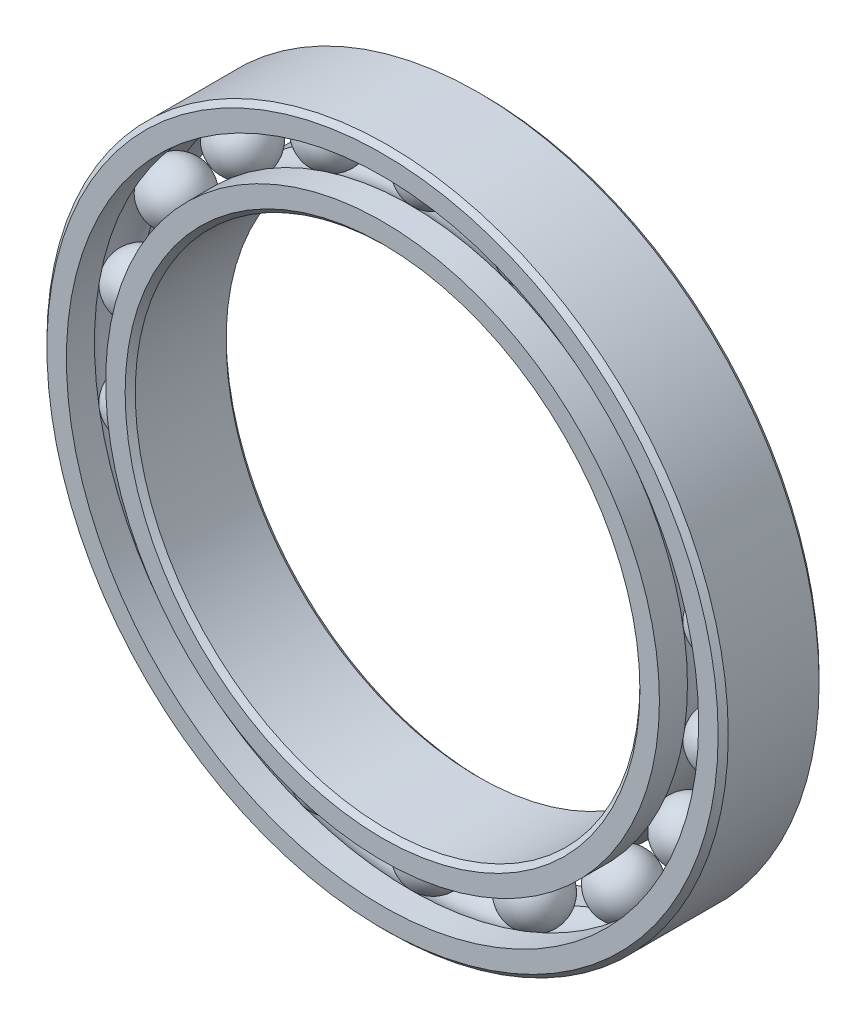
SolidWorks part; units mm, degrees
ref_plane "Front Plane" through (0, 0, 0) normal (0, 0, 1) x (1, 0, 0)
ref_plane "Top Plane" through (0, 0, 0) normal (0, 1, 0) x (1, 0, 0)
ref_plane "Right Plane" through (0, 0, 0) normal (1, 0, 0) x (0, 0, -1)
sketch "Sketch1" plane through (0, 0, 0) normal (0, 0, 1) x (1, 0, 0)
  circle A0 centre (0, 0) radius 13.5
  circle A1 centre (0, 0) radius 10
  dimension "OD" = 27
  dimension "ID" = 20
sketch "Sketch5" plane through (0, 0, 0) normal (1, 0, 0) x (0, 0, -1)
  line L0 (-2, 0) -> (2, 0) construction
  line L1 (0, 13.5) -> (0, -13.5) construction
  line L2 (1.8, 13.5) -> (-1.8, 13.5)
  line L3 (-1.8, 13.5) -> (-2, 13.3)
  line L4 (-2, 13.3) -> (-2, 12.5278)
  line L5 (-2, 12.5278) -> (-0.8889, 12.5278)
  line L6 (2, 12.5278) -> (0.8889, 12.5278)
  line L7 (2, 13.3) -> (2, 12.5278)
  line L8 (1.8, 13.5) -> (2, 13.3)
  line L9 (0, 13.5) -> (0, 11.75) construction
  line L10 (0, 11.75) -> (0, 10) construction
  line L11 (-1.1811, 11.75) -> (-2, 11.75) construction
  line L12 (1.4001, 10.9976) -> (1.7811, 10.9976) construction
  line L13 (-1.4001, 10.9976) -> (-1.7811, 10.9976) construction
  line L14 (-1.4001, 10.9976) -> (-1.4001, 12.5024) construction
  line L15 (-1.4001, 12.5024) -> (-1.7811, 12.5024) construction
  line L16 (-1.7811, 10.9976) -> (-1.7811, 12.5024) construction
  line L17 (-1.4001, 10.9976) -> (-1.7811, 12.5024) construction
  line L18 (-1.4001, 12.5024) -> (-1.7811, 10.9976) construction
  line L19 (1.7811, 10.9976) -> (1.7811, 12.5024) construction
  line L20 (1.4001, 12.5024) -> (1.7811, 12.5024) construction
  line L21 (1.4001, 10.9976) -> (1.4001, 12.5024) construction
  line L22 (0, 13.5) -> (0, -13.5) construction
  arc A0 (-0.8889, 12.5278) -> (0.8889, 12.5278) centre (0, 11.75) cw
  circle A1 centre (0, 11.75) radius 1.1811 construction
  point P14 (0, 10)
  point P15 (-1.5906, 11.75)
  dimension "Width" = 4
  dimension "D1" = 45
  dimension "D2" = 0.2
  dimension "D3" = 1.7778
  dimension "D4" = 0.7778
  dimension "D5" = 0.381
  dimension "D6" = 0.0254
  dimension "D7" = 4
revolve "Revolve1" add sketch "Sketch5" angle 360 about L0
sketch "Sketch3" plane through (0, 0, 0) normal (1, 0, 0) x (0, 0, -1)
  line L0 (-2, 10.9722) -> (-0.8889, 10.9722)
  line L1 (0, 13.5) -> (0, -13.5) construction
  line L2 (-2, 13.3) -> (-2, 12.5278) construction
  line L3 (-2, 10.9722) -> (-2, 10.2)
  line L4 (-1.8, 13.5) -> (-2, 13.3) construction
  line L5 (-2, 10.2) -> (-1.8, 10)
  line L6 (-1.8, 10) -> (1.8, 10)
  line L7 (1.8, 13.5) -> (1.8, -13.5) construction
  line L8 (1.8, 10) -> (2, 10.2)
  line L9 (2, -13.3) -> (2, 13.3) construction
  line L10 (2, 10.2) -> (2, 10.9722)
  line L11 (2, 10.9722) -> (0.8889, 10.9722)
  line L13 (1.8, 13.5) -> (2, 13.3) construction
  arc A0 (0.8889, 12.5278) -> (-0.8889, 12.5278) centre (0, 11.75) ccw construction
  arc A1 (0.8889, 10.9722) -> (-0.8889, 10.9722) centre (0, 11.75) cw
revolve "Revolve3" add sketch "Sketch3" angle 360 about L0
sketch "Sketch4" plane through (0, 0, 0) normal (1, 0, 0) x (0, 0, -1)
  line L0 (-1.1811, 11.75) -> (1.1811, 11.75)
  arc A2 (-1.1811, 11.75) -> (1.1811, 11.75) centre (0, 11.75) cw
  arc A3 (0.8889, 12.5278) -> (-0.8889, 12.5278) centre (0, 11.75) ccw construction
revolve "Revolve4" add sketch "Sketch4" angle 360 about L0
pattern_circular "CirPattern1" count 18 every 20 of bodies 104
ref_axis "Center Axis 1" through (0, 0, -1.8) along (0, 0, 1)
equation "\"D2@Sketch5\" = \"Width@Sketch5\" * .05"
equation "\"D3@Sketch5\" = \"Width@Sketch5\" / 2.25"
equation "\"D4@Sketch5\"=((\"OD@Sketch1\"-\"ID@Sketch1\")/2)/4.5"
equation "\"D2@CirPattern1\" = 360/\"Balls@CirPattern1\""
